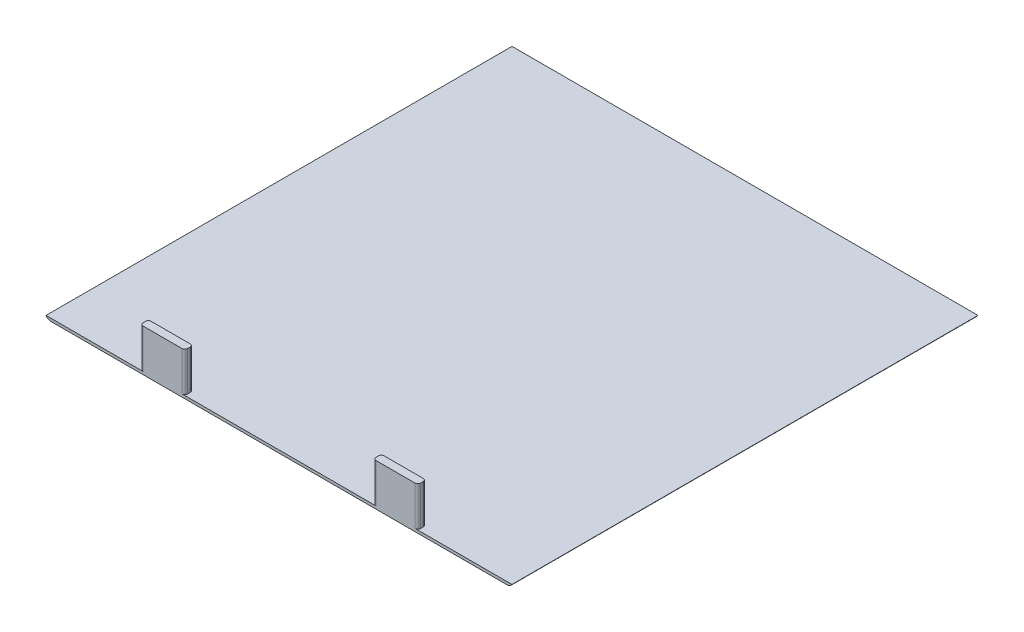
SolidWorks part; units mm, degrees
ref_plane "Front Plane" through (0, 0, 0) normal (0, 0, 1) x (1, 0, 0)
ref_plane "Top Plane" through (0, 0, 0) normal (0, 1, 0) x (1, 0, 0)
ref_plane "Right Plane" through (0, 0, 0) normal (1, 0, 0) x (0, 0, -1)
sketch "Sketch1" plane through (0, 0, 0) normal (0, 1, 0) x (1, 0, 0)
  line L1 (-105.41, 105.41) -> (105.41, 105.41)
  line L2 (-105.41, 105.41) -> (-105.41, -105.41)
  line L3 (-105.41, -105.41) -> (105.41, -105.41)
  line L4 (105.41, 105.41) -> (105.41, -105.41)
  line L5 (-105.41, 105.41) -> (105.41, -105.41) construction
  line L6 (-105.41, -105.41) -> (105.41, 105.41) construction
  point P0 (0, 0)
  dimension "D1" = 210.82
  dimension "D2" = 210.82
extrude "Boss-Extrude1" add sketch "Sketch1" along normal blind 1.27
sketch "Sketch2" plane through (0, 1.27, 0) normal (0, 1, 0) x (1, 0, 0)
  line L0 (-105.41, -105.41) -> (105.41, -105.41) construction
  line L1 (0, 0) -> (0, -105.41) construction
  line L2 (-105.41, 0) -> (0, 0) construction
  line L3 (-105.41, 105.41) -> (-105.41, -105.41) construction
  line L4 (42.6085, -102.997) -> (42.6085, -104.14)
  line L5 (-61.5315, -101.727) -> (-43.8785, -101.727)
  line L6 (-62.8015, -102.997) -> (-62.8015, -104.14)
  line L7 (-61.5315, -105.41) -> (-43.8785, -105.41)
  line L8 (-42.6085, -102.997) -> (-42.6085, -104.14)
  line L9 (-62.8015, -101.727) -> (-42.6085, -105.41) construction
  line L10 (-62.8015, -105.41) -> (-42.6085, -101.727) construction
  line L11 (61.5315, -105.41) -> (43.8785, -105.41)
  line L12 (62.8015, -102.997) -> (62.8015, -104.14)
  line L13 (61.5315, -101.727) -> (43.8785, -101.727)
  arc A0 (-43.8785, -101.727) -> (-42.6085, -102.997) centre (-43.8785, -102.997) cw
  arc A1 (-43.8785, -105.41) -> (-42.6085, -104.14) centre (-43.8785, -104.14) ccw
  arc A2 (-62.8015, -104.14) -> (-61.5315, -105.41) centre (-61.5315, -104.14) ccw
  arc A3 (-61.5315, -101.727) -> (-62.8015, -102.997) centre (-61.5315, -102.997) ccw
  arc A4 (43.8785, -101.727) -> (42.6085, -102.997) centre (43.8785, -102.997) ccw
  arc A5 (43.8785, -105.41) -> (42.6085, -104.14) centre (43.8785, -104.14) cw
  arc A6 (62.8015, -104.14) -> (61.5315, -105.41) centre (61.5315, -104.14) cw
  arc A7 (61.5315, -101.727) -> (62.8015, -102.997) centre (61.5315, -102.997) cw
  point P11 (-52.705, -103.5685)
  point P18 (-52.705, 0)
  dimension "D2" = 1.27
  dimension "D1" = 3.683
  dimension "D3" = 20.193
extrude "Boss-Extrude2" add sketch "Sketch2" along normal blind 17.78
sketch "Sketch3" plane through (0, 0, 0) normal (0, -1, 0) x (1, 0, 0)
  line L4 (-101.6, 101.6) -> (-101.6, -101.6)
  line L5 (-101.6, -101.6) -> (101.6, -101.6)
  line L6 (101.6, -101.6) -> (101.6, 101.6)
  line L7 (101.6, 101.6) -> (-101.6, 101.6)
  line L8 (102.87, -102.87) -> (102.87, 102.87)
  line L9 (102.87, 102.87) -> (-102.87, 102.87)
  line L10 (-102.87, 102.87) -> (-102.87, -102.87)
  line L11 (-102.87, -102.87) -> (102.87, -102.87)
  line L12 (102.87, -102.87) -> (102.87, 102.87)
  line L13 (102.87, 102.87) -> (-102.87, 102.87)
  line L14 (-102.87, 102.87) -> (-102.87, -102.87)
  line L15 (-102.87, -102.87) -> (102.87, -102.87)
  dimension "D1" = 2.54
  dimension "D2" = 1.27
extrude "Boss-Extrude3" add sketch "Sketch3" along normal blind 0.508
fillet "Fillet1" radius 2.54 3 edges at (105.41, 0, 0) (0, 0, -105.41) (-105.41, 0, 0)
fillet "Fillet2" radius 2.54 4 edges at (0, -0.508, 102.87) (102.87, -0.508, 0) (0, -0.508, -102.87) (-102.87, -0.508, 0)
